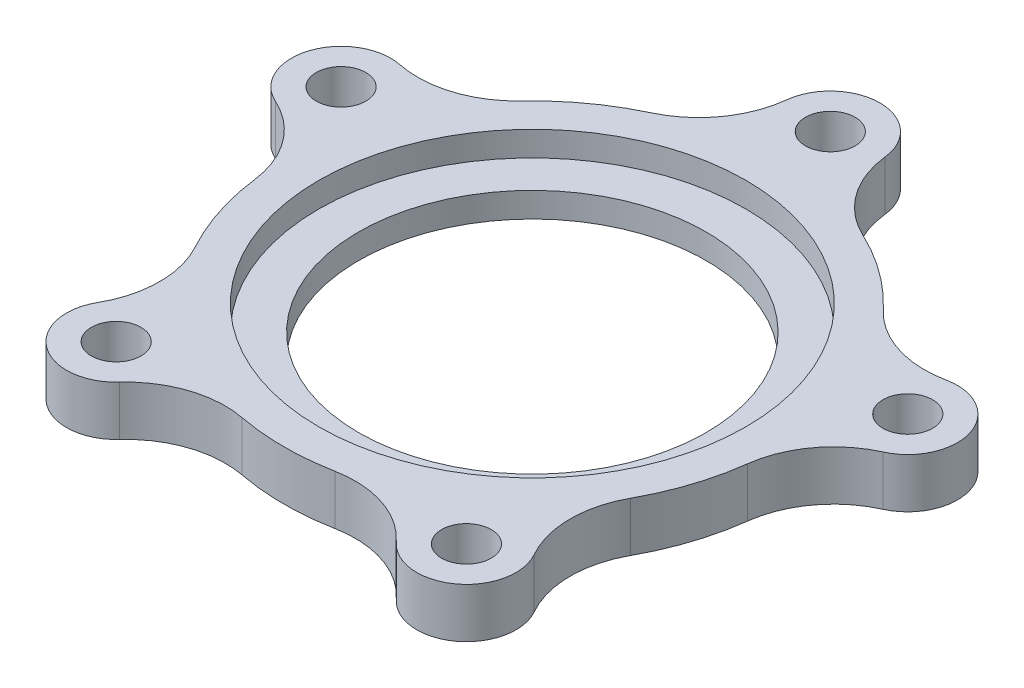
SolidWorks part; units mm, degrees
note: The reader was unsure of these and kept them because the rebuilt part matched: shared geometry of "Sketch1<6>".
ref_plane "Front Plane" through (0, 0, 0) normal (0, 0, 1) x (1, 0, 0)
ref_plane "Top Plane" through (0, 0, 0) normal (0, 1, 0) x (1, 0, 0)
ref_plane "Right Plane" through (0, 0, 0) normal (1, 0, 0) x (0, 0, -1)
sketch "Sketch1" plane through (0, 0, 0) normal (0, 1, 0) x (1, 0, 0)
  line L0 (0, 0) -> (0, 38.1) construction
  line L1 (6.35, 38.1) -> (6.35, 31.1085)
  line L2 (-6.35, 38.1) -> (-6.35, 31.1085)
  line L3 (34.273, 17.8128) -> (27.6237, 15.6523)
  line L4 (38.1975, 5.7343) -> (31.5482, 3.5739)
  line L5 (27.5319, -27.0911) -> (23.4224, -21.4349)
  line L6 (17.2574, -34.556) -> (13.1479, -28.8998)
  line L7 (-17.2574, -34.556) -> (-13.1479, -28.8998)
  line L8 (-27.5319, -27.0911) -> (-23.4224, -21.4349)
  line L9 (-38.1975, 5.7343) -> (-31.5482, 3.5739)
  line L10 (-34.273, 17.8128) -> (-27.6237, 15.6523)
  circle A0 centre (0, 0) radius 31.75
  circle A1 centre (0, 0) radius 27.305
  circle A2 centre (0, 38.1) radius 3.175
  circle A4 centre (0, 0) radius 22.225
  circle A5 centre (0, 38.1) radius 6.35
  circle A6 centre (36.2353, 11.7735) radius 6.35
  circle A7 centre (36.2353, 11.7735) radius 3.175
  circle A8 centre (22.3946, -30.8235) radius 6.35
  circle A9 centre (22.3946, -30.8235) radius 3.175
  circle A10 centre (-22.3946, -30.8235) radius 6.35
  circle A11 centre (-22.3946, -30.8235) radius 3.175
  circle A12 centre (-36.2353, 11.7735) radius 6.35
  circle A13 centre (-36.2353, 11.7735) radius 3.175
  point P22 (0, 0)
  point P25 (0, 0)
  point P44 (0, 0)
  dimension "D1" = 6.35
  dimension "D2" = 38.1
  dimension "D3" = 54.61
  dimension "D4" = 63.5
  dimension "D5" = 44.45
  dimension "D6" = 12.7
  dimension "D7" = 5
  dimension "D8" = 5
extrude "Boss-Extrude4" add sketch "Sketch1" along normal blind 6.35 contours A6 A0 A5 A1 | L0 A1 A5 A0 A2 | A0 A5 A2 | A1 L0 A2 A0 A5 | A12 A1 A5 A0 | A13 A0 A12 A1 | A13 A0 A12 | A12 A0 A10 A1 | A11 A0 A10 A1 | A11 A0 A10 | A9 A0 A8 A1 | A9 A0 A8 | A10 A0 A8 A1 | A8 A0 A6 A1 | A7 A0 A6 A1 | A7 A0 A6
extrude "Boss-Extrude5" add sketch "Sketch1<6>" along normal blind 3.175
sketch "Sketch1<6>" plane through (0, 0, 0) normal (0, 1, 0) x (1, 0, 0) same geometry as "Sketch1"
fillet "Fillet2" radius 12.7 10 edges at (27.6237, 3.175, -15.6523) (31.5482, 3.175, -3.5739) (23.4224, 3.175, 21.4349) (13.1479, 3.175, 28.8998) (-13.1479, 3.175, 28.8998) (-23.4224, 3.175, 21.4349) (-31.5482, 3.175, -3.5739) (-27.6237, 3.175, -15.6523) (-6.35, 3.175, -31.1085) (6.35, 3.175, -31.1085)
